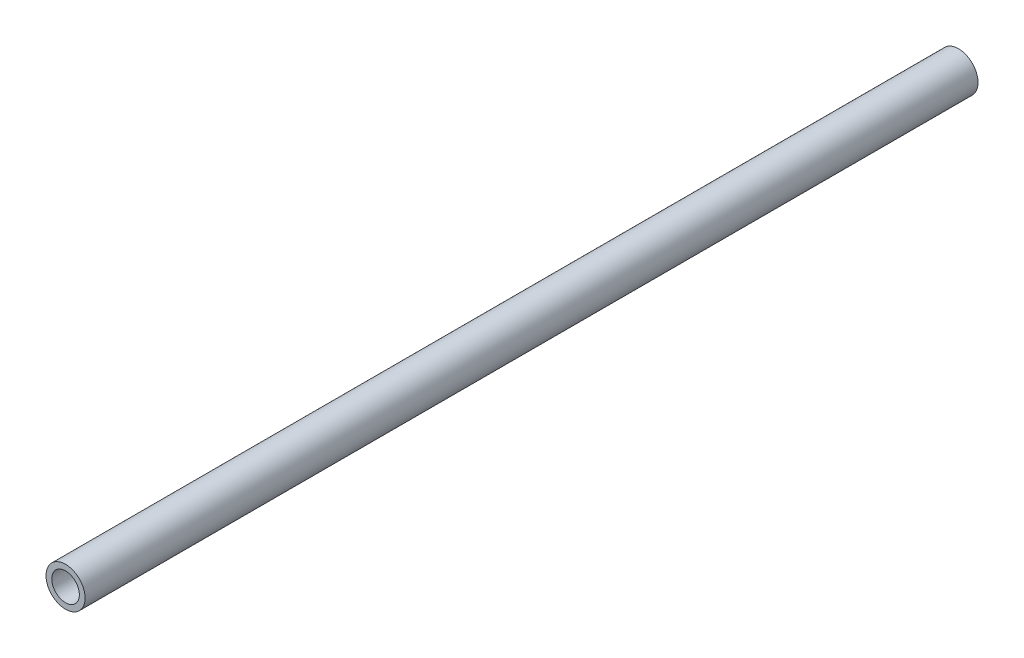
SolidWorks part; units mm, degrees
ref_plane "Front Plane" through (0, 0, 0) normal (0, 0, 1) x (1, 0, 0)
ref_plane "Top Plane" through (0, 0, 0) normal (0, 1, 0) x (1, 0, 0)
ref_plane "Right Plane" through (0, 0, 0) normal (1, 0, 0) x (0, 0, -1)
sketch "Sketch1" plane through (0, 0, 0) normal (0, 0, 1) x (1, 0, 0)
  circle A0 centre (0, 0) radius 13.335
  dimension "Pipe OD" = 26.67
extrude "Extrude-Thin1" add sketch "Sketch1" along normal mid plane 609.6 thin thin type one direction reverse wall 3.9116
